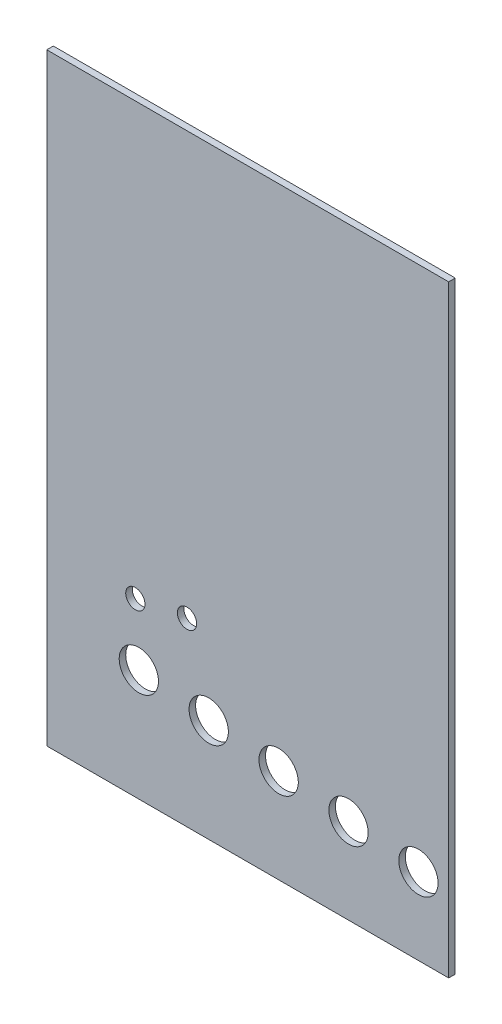
SolidWorks part; units mm, degrees
material "Polypropylene"
ref_plane "Front Plane" through (0, 0, 0) normal (0, 0, 1) x (1, 0, 0)
ref_plane "Top Plane" through (0, 0, 0) normal (0, 1, 0) x (1, 0, 0)
ref_plane "Right Plane" through (0, 0, 0) normal (1, 0, 0) x (0, 0, -1)
sketch "Sketch1" plane through (0, 0, 0) normal (0, 0, 1) x (1, 0, 0)
  line L0 (64.3744, -313.2564) -> (64.3744, -356.9444) construction
  line L1 (0, 0) -> (292.1, 0)
  line L2 (0, 0) -> (0, -438.15)
  line L3 (0, -438.15) -> (292.1, -438.15)
  line L4 (292.1, 0) -> (292.1, -438.15)
  line L5 (64.3744, -313.2564) -> (101.9257, -306.8134) construction
  line L6 (64.3744, -313.2564) -> (101.9257, -313.2564) construction
  line L7 (101.9257, -313.2564) -> (101.9257, -306.8134) construction
  line L8 (64.3744, -356.9444) -> (66.9144, -356.9444) construction
  line L9 (66.9144, -356.9444) -> (117.7144, -356.9444) construction
  line L10 (117.7144, -356.9444) -> (117.7144, -363.2944) construction
  line L11 (117.7144, -363.2944) -> (168.5144, -363.2944) construction
  line L12 (168.5144, -363.2944) -> (168.5144, -369.6444) construction
  line L13 (168.5144, -369.6444) -> (219.3144, -369.6444) construction
  line L14 (219.3144, -369.6444) -> (219.3144, -375.9944) construction
  line L15 (219.3144, -375.9944) -> (270.1144, -375.9944) construction
  line L16 (270.1144, -375.9944) -> (270.1144, -382.3444) construction
  circle A0 centre (101.9257, -306.8134) radius 7
  circle A1 centre (64.3744, -313.2564) radius 7
  circle A2 centre (66.9144, -356.9444) radius 14.2875
  circle A3 centre (117.7144, -363.2944) radius 14.2875
  circle A4 centre (168.5144, -369.6444) radius 14.2875
  circle A5 centre (219.3144, -375.9944) radius 14.2875
  circle A6 centre (270.1144, -382.3444) radius 14.2875
  dimension "D3" = 14
  dimension "D6" = 43.688
  dimension "D8" = 28.575
  dimension "D9" = 28.575
  dimension "D10" = 28.575
  dimension "D17" = 28.575
  dimension "D19" = 28.575
  dimension "D1" = 438.15
  dimension "D2" = 292.1
  dimension "D4" = 38.1
  dimension "D5" = 9.736
  dimension "D7" = 2.54
  dimension "D11" = 50.8
  dimension "D12" = 50.8
  dimension "D13" = 6.35
  dimension "D14" = 50.8
  dimension "D15" = 6.35
  dimension "D16" = 6.35
  dimension "D18" = 50.8
extrude "Boss-Extrude1" add sketch "Sketch1" along normal blind 4.7625
